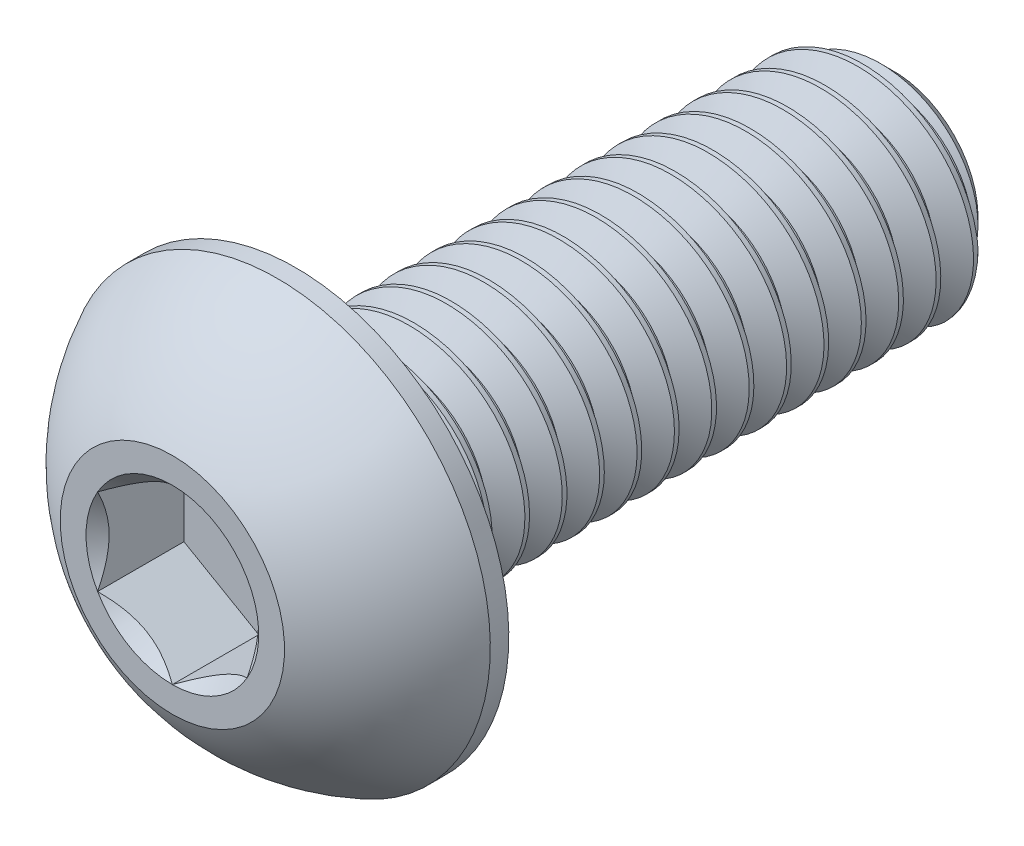
SolidWorks part; units mm, degrees
ref_plane "Front" through (0, 0, 0) normal (0, 0, 1) x (1, 0, 0)
ref_plane "Top" through (0, 0, 0) normal (0, 1, 0) x (1, 0, 0)
ref_plane "Right" through (0, 0, 0) normal (1, 0, 0) x (0, 0, -1)
sketch "Sketch1" plane through (0, 0, 0) normal (1, 0, 0) x (0, 0, -1)
  line L2 (-4, 1.5) -> (4, 1.5)
  line L3 (4, 1.5) -> (4, 0)
  line L4 (4, 0) -> (-4, 0)
  line L6 (-4.2475, 2.85) -> (-4, 2.85) construction
  line L7 (4, 1.5) -> (4, -1.5) construction
  line L8 (-5.65, 0) -> (-4, 0) construction
  line L9 (-4, 2.85) -> (-4, -2.85) construction
  line L11 (-4, 1.5) -> (-4, 0)
  line L13 (-5.65, 1) -> (-5.65, -1) construction
  line L14 (-5.65, 1) -> (-5.65, 1.5) construction
  line L15 (3.9688, 1.5541) -> (4.2188, 1.1211) construction
  line L16 (4.2188, 1.1211) -> (4.4688, 1.5541) construction
  line L17 (4.4688, 1.5541) -> (3.9688, 1.5541) construction
  line L18 (4, 1.5) -> (4.4375, 1.5) construction
  line L19 (4.2188, 1.5541) -> (4.2188, 1.5) construction
  line L20 (4.2188, 1.5) -> (4.2188, 1.1752) construction
  line L21 (4.2188, 1.1752) -> (4.2188, 1.1211) construction
  line L22 (4.1875, 1.1752) -> (4.25, 1.1752)
  line L23 (3.9844, 1.5271) -> (4.4531, 1.5271)
  line L24 (4.25, 1.1752) -> (4.4531, 1.5271)
  line L25 (4.1875, 1.1752) -> (3.9844, 1.5271)
  line L26 (3.625, 1.5) -> (4, 1.125)
  arc A3 (-5.65, 1.5) -> (-4.2475, 2.85) centre (-2.8552, 0) cw construction
  point P29 (4.2187, 1.5271)
  point P30 (2.75, -1.5)
  point P33 (0, 0)
  dimension "Thread Size" = 3
  dimension "D1" = 0.2475
  dimension "Head Height" = 1.65
  dimension "Head Diameter" = 5.7
  dimension "Length" = 8
  dimension "Drive Size" = 2
  dimension "Thread Pitch" = 0.5
  dimension "D3" = 0.0625
  dimension "D2" = 0.375
  dimension "D4" = 45
  dimension "D5" = 1.25
sketch "Sketch10" plane through (0, 0, 0) normal (1, 0, 0) x (0, 0, -1)
  line L0 (3.625, 1.5) -> (4, 1.125) construction
  line L1 (3.625, 1.5) -> (4, 1.125)
  line L4 (4, 1.5) -> (-4, 1.5)
  line L5 (4, 0) -> (4, 1.5)
  line L6 (-4, 0) -> (4, 0)
  line L7 (-4, 1.5) -> (-4, 0)
  line L8 (3.625, 1.5) -> (-4, 1.5)
  line L9 (4, 0) -> (4, 1.125)
  line L10 (-4, 0) -> (4, 0)
  line L11 (-4, 1.5) -> (-4, 0)
  dimension "D1" = 0
revolve "Revolve3" add sketch "Sketch10" angle 360 about L8
sketch "Sketch7" plane through (0, 0, 0) normal (1, 0, 0) x (0, 0, -1)
  line L6 (-4.2475, 2.85) -> (-4, 2.85) construction
  line L8 (-5.65, 0) -> (-4, 0) construction
  line L11 (-4, 2.85) -> (-4, -2.85) construction
  line L12 (-4.2475, 2.85) -> (-4, 2.85)
  line L13 (-5.65, 0) -> (-4, 0)
  line L14 (-5.65, 1) -> (-5.65, -1) construction
  line L15 (-4, 2.85) -> (-4, 0)
  line L16 (-5.65, 1.5) -> (-5.65, 0)
  arc A2 (-4.2475, 2.85) -> (-5.65, 1.5) centre (-2.8552, 0) ccw construction
  arc A3 (-4.2475, 2.85) -> (-5.65, 1.5) centre (-2.8552, 0) ccw
revolve "Revolve2" add sketch "Sketch7" angle 360 mid plane about L13
sketch "Sketch5" plane through (0, 0, 5.65) normal (0, 0, 1) x (1, 0, 0)
  line L1 (1, -0.5774) -> (1, 0.5774)
  line L2 (1, 0.5774) -> (0, 1.1547)
  line L3 (0, 1.1547) -> (-1, 0.5774)
  line L4 (-1, 0.5774) -> (-1, -0.5774)
  line L5 (-1, -0.5774) -> (0, -1.1547)
  line L6 (0, -1.1547) -> (1, -0.5774)
  circle A0 centre (0, 0) radius 1 construction
extrude "Cut-Extrude2" cut sketch "Sketch5" against normal blind 1.155
sketch "Sketch6" plane through (0, 0, 5.65) normal (0, 0, 1) x (1, 0, 0)
  circle A0 centre (0, 0) radius 1.1547
extrude "Cut-Extrude3" cut sketch "Sketch6" against normal blind 1.155 draft 45
sketch "Sketch9" plane through (0, 0, 4) normal (0, 0, -1) x (-1, 0, 0)
  circle A0 centre (0, 0) radius 1.5 construction
  circle A4 centre (0, 0) radius 1.5
split "Split1" bodies to split 113 resulting bodies 123 124 split by face at (0, -2.85, 4)
sketch "Sketch11" plane through (0, 0, -4) normal (0, 0, -1) x (-1, 0, 0)
  circle A0 centre (0, 0) radius 1.5 construction
  circle A1 centre (0, 0) radius 1.5
curve "Helix/Spiral1" pitch 0.5 height 9.65 radius 1.5 centre (0, 0, -4) axis (0, 0, 1) start towards (0, 1, 0)
sketch "Sketch12" plane through (0, 0, 0) normal (1, 0, 0) x (0, 0, -1)
  line L0 (4.1875, 1.1752) -> (4.25, 1.1752) construction
  line L1 (4.25, 1.1752) -> (4.4531, 1.5271) construction
  line L2 (3.9844, 1.5271) -> (4.4531, 1.5271) construction
  line L3 (4.1875, 1.1752) -> (3.9844, 1.5271) construction
  line L4 (4.1875, 1.1752) -> (4.25, 1.1752)
  line L5 (4.25, 1.1752) -> (4.4531, 1.5271)
  line L6 (3.9844, 1.5271) -> (4.4531, 1.5271)
  line L7 (4.1875, 1.1752) -> (3.9844, 1.5271)
sweep "Cut-Sweep2" cut profiles "Sketch12" path "Helix/Spiral1" align with end faces yes
extrude "Boss-Extrude1" add sketch "Sketch9" along normal blind 10 draft 45
equation "\"D1@Cut-Extrude2\" = \"Head Height@Sketch1\" * .7"
equation "\"D1@Sketch1\" = \"Head Height@Sketch1\" * .15"
equation "\"D1@Cut-Extrude3\" = \"D1@Cut-Extrude2\""
equation "\"D3@Sketch1\" = \"Thread Pitch@Sketch1\" / 8"
equation "\"D2@Sketch1\" = \"Thread Pitch@Sketch1\" * 0.75"
equation "\"D3@Helix/Spiral1\" = \"Length@Sketch1\" + \"Head Height@Sketch1\""
equation "\"D4@Helix/Spiral1\" = \"Thread Pitch@Sketch1\""
equation "\"D5@Sketch1\" = \"Thread Pitch@Sketch1\" * 2.5"
